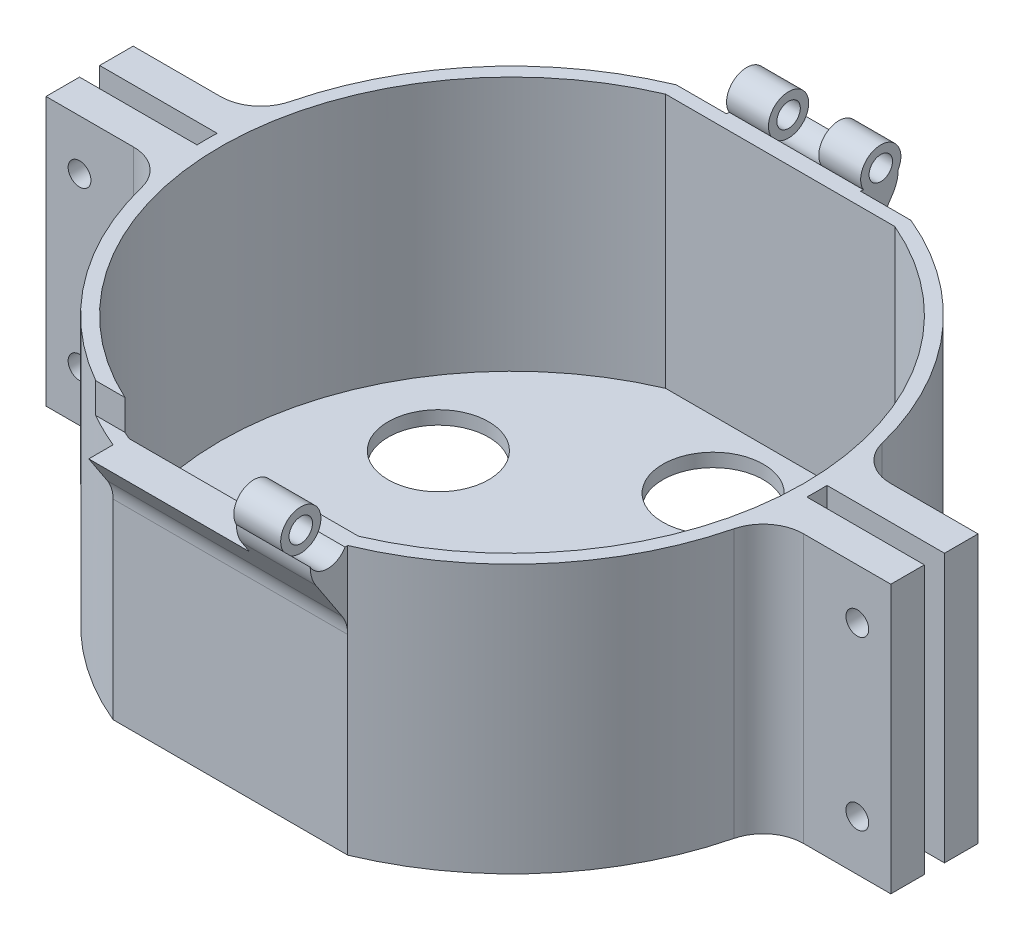
SolidWorks part; units mm, degrees
ref_plane "Front Plane" through (0, 0, 0) normal (0, 0, 1) x (1, 0, 0)
ref_plane "Top Plane" through (0, 0, 0) normal (0, 1, 0) x (1, 0, 0)
ref_plane "Right Plane" through (0, 0, 0) normal (1, 0, 0) x (0, 0, -1)
sketch "Sketch1" plane through (0, 0, 0) normal (0, 1, 0) x (1, 0, 0)
  line L0 (-17.5, 42) -> (17.5, 42)
  line L1 (-17.5, -42) -> (17.5, -42)
  line L2 (0, 0) -> (35.5206, 0) construction
  arc A0 (-17.5, 42) -> (-17.5, -42) centre (0, 0) ccw
  arc A1 (17.5, -42) -> (17.5, 42) centre (0, 0) ccw
  dimension "D1" = 91
  dimension "D2" = 42
  dimension "D3" = 42
extrude "Boss-Extrude1" add sketch "Sketch1" along normal blind 40
shell "Shell1" thickness 2 removed face at (0, 40, 0)
sketch "Sketch2" plane through (0, 2, 0) normal (0, 1, 0) x (1, 0, 0)
  circle A0 centre (0, 0) radius 3
  circle A1 centre (0, 30) radius 7.5
  circle A2 centre (25.9808, 15) radius 7.5
  circle A3 centre (25.9808, -15) radius 7.5
  circle A4 centre (0, -30) radius 7.5
  circle A5 centre (-25.9808, -15) radius 7.5
  circle A6 centre (-25.9808, 15) radius 7.5
  point P18 (0, 0)
  dimension "D1" = 6
  dimension "D2" = 15
  dimension "D3" = 30
  dimension "D4" = 6
extrude "Cut-Extrude1" cut sketch "Sketch2" against normal up to surface (2 mm away) up to face at (0, 0, 0)
sketch "Sketch3" plane through (0, 0, 0) normal (0, -1, 0) x (1, 0, 0)
  line L2 (0, 0) -> (-50.0606, 50.0606) construction
  line L3 (0, 0) -> (-30.2903, 0) construction
  line L4 (-35.8503, 28.0179) -> (-41.5072, 35.8503)
  line L5 (-41.5072, 35.8503) -> (-41.5072, 41.5072)
  line L6 (-41.5072, 41.5072) -> (-35.8503, 41.5072)
  line L7 (-35.8503, 41.5072) -> (-28.0179, 35.8503)
  arc A0 (-35.8503, 28.0179) -> (-28.0179, 35.8503) centre (0, 0) cw
  circle A1 centre (0, 0) radius 45.5 construction
  circle A2 centre (-35.8503, 35.8503) radius 3
  dimension "D2" = 6
  dimension "D1" = 45
  dimension "D3" = 50.7
  dimension "D4" = 8
extrude "Boss-Extrude2" [suppressed] add sketch "Sketch3" against normal blind 10
fillet "Fillet1" [suppressed] radius 5
pattern_circular "CirPattern1" [suppressed] count 4 over 360 of bodies 103
sketch "Sketch4" plane through (0, 0, 0) normal (1, 0, 0) x (0, 0, -1)
  line L0 (-42, 30) -> (-47.5981, 38.5)
  line L1 (-42, 40) -> (-42, 0) construction
  line L2 (-47.5981, 38.5) -> (-47.5981, 40)
  line L3 (-42.4019, 40) -> (-42, 40)
  line L4 (-42, 40) -> (-42, 30)
  line L5 (-42, 40) -> (-42, 44.2633) construction
  line L6 (-45, 38.5) -> (-46.9312, 38.5) construction
  arc A0 (-42.4019, 40) -> (-47.5981, 40) centre (-45, 41.5) ccw
  circle A1 centre (-45, 41.5) radius 1.75
  dimension "D1" = 6
  dimension "D2" = 3.5
  dimension "D3" = 10
  dimension "D4" = 5.5981
  dimension "D5" = 1.5
extrude "Boss-Extrude3" add sketch "Sketch4" along normal up to vertex (17.5 mm away) and the other way up to vertex (17.5 mm away) up to point (17.5, 40, 42) other way up to point (-17.5, 40, 42)
fillet "Fillet2" radius 5 2 edges at (0, 38.5, 47.5981) (0, 30, 42)
mirror "Mirror1" about plane through (0, 0, 0) normal (0, 0, 1) of "Boss-Extrude3"
fillet "Fillet3" radius 5 2 edges at (0, 38.5, -47.5981) (0, 30, -42)
sketch "Sketch5" plane through (17.5, 0, 0) normal (1, 0, 0) x (0, 0, -1)
  circle A1 centre (-45, 41.5) radius 3
extrude "Cut-Extrude2" cut sketch "Sketch5" against normal blind 4
sketch "Sketch6" plane through (0, 0, 0) normal (1, 0, 0) x (0, 0, -1)
  circle A1 centre (45, 41.5) radius 3
extrude "Cut-Extrude3" cut sketch "Sketch6" against normal blind 3.75 and the other way blind 3.75
sketch "Sketch7" plane through (-17.5, 0, 0) normal (-1, 0, 0) x (0, 0, 1)
  line L1 (-42, 28.5014) -> (-52, 28.5014)
  line L2 (-42, 28.5014) -> (-42, 48.5014)
  line L3 (-42, 48.5014) -> (-52, 48.5014)
  line L4 (-52, 28.5014) -> (-52, 48.5014)
  dimension "D1" = 10
  dimension "D2" = 20
extrude "Cut-Extrude4" cut sketch "Sketch7" against normal blind 7.5
sketch "Sketch8" plane through (-17.5, 0, 0) normal (-1, 0, 0) x (0, 0, 1)
  line L0 (45, 41.5) -> (51.7755, 41.5) construction
  line L5 (39.5, 35.5) -> (50.5, 35.5)
  line L6 (39.5, 35.5) -> (39.5, 47.5)
  line L7 (39.5, 47.5) -> (50.5, 47.5)
  line L8 (50.5, 35.5) -> (50.5, 47.5)
  line L9 (45, 41.5) -> (45, 46.629) construction
  point P5 (45, 35.5)
  point P9 (50.5, 41.5)
  dimension "D1" = 11
  dimension "D2" = 12
sketch "Sketch9" plane through (17.5, 0, 0) normal (1, 0, 0) x (0, 0, -1)
  line L0 (42, 28.5014) -> (42, 0) construction
  line L1 (42, 25.5014) -> (52, 25.5014)
  line L2 (42, 25.5014) -> (42, 50.5014)
  line L3 (42, 50.5014) -> (52, 50.5014)
  line L4 (52, 25.5014) -> (52, 50.5014)
  dimension "D1" = 10
  dimension "D2" = 25
  dimension "D3" = 3
extrude "Cut-Extrude6" cut sketch "Sketch9" against normal blind 7.5
extrude "Cut-Extrude7" cut sketch "Sketch8" against normal blind 24 and the other way up to surface other way up to face at (-28.7, 21.7003, 8.4)
fillet "Fillet4" [suppressed] radius 5
sketch "Sketch10" plane through (0, 0, 0) normal (0, -1, 0) x (1, 0, 0)
  line L0 (0, 0) -> (78.512, 0) construction
  line L1 (45.4753, 1.5) -> (63, 1.5)
  line L2 (63, 1.5) -> (63, 6.5)
  line L3 (63, 6.5) -> (49.96, 6.5)
  line L4 (0, 0) -> (0, 52.8713) construction
  arc A0 (17.5, -42) -> (17.5, 42) centre (0, 0) ccw construction
  arc A1 (49.96, 6.5) -> (44.1394, 11.0437) centre (49.96, 12.5) cw
  arc A2 (45.4753, 1.5) -> (44.1394, 11.0437) centre (0, 0) ccw
  dimension "D4" = 6
  dimension "D1" = 3
  dimension "D2" = 5
  dimension "D3" = 126
extrude "Boss-Extrude4" add sketch "Sketch10" against normal up to surface (40 mm away) up to face at (2.2771, 40, -5.075)
hole_wizard "M3 Clearance Hole1" positions "Sketch11" profile "Sketch12" hole size "M3" standard "ANSI Metric" end condition through all
sketch "Sketch11" plane through (0, 0, 6.5) normal (0, 0, 1) x (1, 0, 0)
  line L0 (63, 20) -> (80.4921, 20) construction
  line L1 (63, 40) -> (63, 0) construction
  point P9 (58, 32.5)
  point P11 (58, 7.5)
  dimension "D1" = 25
  dimension "D2" = 5
sketch "Sketch12" plane through (58, 7.5, 6.5) normal (1, 0, 0) x (0, -1, 0)
  line L0 (0, 0) -> (0, 54.5)
  line L1 (0, 54.5) -> (1.7, 54.5)
  line L2 (1.7, 54.5) -> (1.7, 0)
  line L5 (1.7, 0) -> (0, 0)
  line L11 (0, -6.35) -> (0, 107.95) construction
  dimension "Thru Hole Dia." = 3.4
  dimension "Thru Hole Depth" = 54.5
mirror "Mirror2" about plane through (0, 0, 0) normal (1, 0, 0) of "M3 Clearance Hole1", "Boss-Extrude4" second plane through (0, 0, 0) second plane normal (0, 0, 1)
